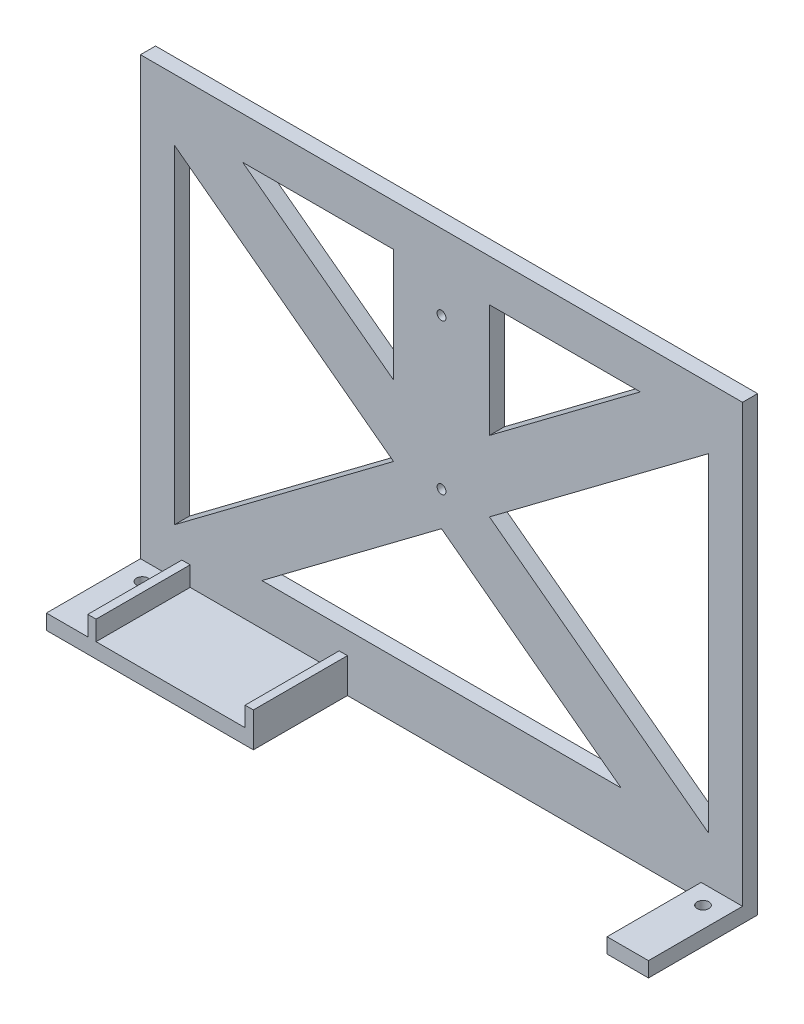
SolidWorks part; units mm, degrees
ref_plane "Front" through (0, 0, 0) normal (0, 0, 1) x (1, 0, 0)
ref_plane "Top" through (0, 0, 0) normal (0, 1, 0) x (1, 0, 0)
ref_plane "Right" through (0, 0, 0) normal (1, 0, 0) x (0, 0, -1)
sketch "Sketch1" plane through (0, 0, 0) normal (0, 0, 1) x (1, 0, 0)
  line L0 (-90.1289, 55.4552) -> (-90.1289, -55.4552)
  line L1 (-101.6, 76.2) -> (101.6, 76.2)
  line L2 (-101.6, 76.2) -> (-101.6, -76.2)
  line L3 (-101.6, -76.2) -> (101.6, -76.2)
  line L4 (101.6, 76.2) -> (101.6, -76.2)
  line L5 (-101.6, 76.2) -> (101.6, -76.2) construction
  line L6 (-101.6, -76.2) -> (101.6, 76.2) construction
  line L7 (0, -55) -> (0, 55) construction
  line L8 (-90.1289, -55.4552) -> (-16.1887, 0)
  line L9 (-16.1887, 0) -> (-90.1289, 55.4552)
  line L10 (55, 0) -> (-55, 0) construction
  line L11 (16.1887, 0) -> (90.1289, 55.4552)
  line L12 (90.1289, -55.4552) -> (16.1887, 0)
  line L13 (90.1289, 55.4552) -> (90.1289, -55.4552)
  line L14 (-16.1887, 61.9912) -> (-16.1887, 23.8125)
  line L15 (-16.1887, 23.8125) -> (-67.0937, 61.9912)
  line L16 (-67.0937, 61.9912) -> (-16.1887, 61.9912)
  line L17 (16.1887, 23.8125) -> (67.0937, 61.9912)
  line L18 (16.1887, 61.9912) -> (16.1887, 23.8125)
  line L19 (67.0937, 61.9912) -> (16.1887, 61.9912)
  line L20 (-60.6282, -57.0175) -> (0, -11.5463)
  line L21 (0, -11.5463) -> (60.6282, -57.0175)
  line L22 (60.6282, -57.0175) -> (-60.6282, -57.0175)
  circle A0 centre (0, 50.8) radius 1.5
  circle A2 centre (0, 0) radius 1.5
  point P0 (0, 0)
  dimension "D3" = 3
  dimension "D4" = 50.8
  dimension "D6" = 19.05
  dimension "D1" = 203.2
  dimension "D2" = 152.4
  dimension "D5" = 25.4
extrude "Boss-Extrude1" add sketch "Sketch1" along normal blind 5.08 contours L4 L1 L2 L3 A2 A0 L19 L17 L18 L9 L8 L0 L11 L13 L12 L15 L16 L14 L21 L22 L20 region at (0, 73.66, 0)
sketch "Sketch2" plane through (0, 0, 5.08) normal (0, 0, 1) x (1, 0, 0)
  line L0 (-101.6, -76.2) -> (101.6, -76.2) construction
  line L1 (-101.6, -76.2) -> (-87.63, -76.2)
  line L2 (-101.6, -76.2) -> (-101.6, -71.12)
  line L3 (-101.6, -71.12) -> (-87.63, -71.12)
  line L4 (-87.63, -76.2) -> (-87.63, -71.12)
  line L5 (0, -55) -> (0, 55) construction
  line L6 (101.6, -71.12) -> (87.63, -71.12)
  line L7 (87.63, -76.2) -> (87.63, -71.12)
  line L8 (101.6, -76.2) -> (87.63, -76.2)
  line L9 (101.6, -76.2) -> (101.6, -71.12)
  line L11 (-87.63, -71.12) -> (-31.75, -71.12)
  line L12 (-87.63, -71.12) -> (-87.63, -76.2)
  line L13 (-87.63, -76.2) -> (-31.75, -76.2)
  line L14 (-31.75, -71.12) -> (-31.75, -76.2)
  line L15 (-87.63, -71.12) -> (-84.836, -71.12)
  line L16 (-87.63, -71.12) -> (-87.63, -64.5258)
  line L17 (-87.63, -64.5258) -> (-84.836, -64.5258)
  line L18 (-84.836, -71.12) -> (-84.836, -64.5258)
  line L19 (-31.75, -71.12) -> (-34.544, -71.12)
  line L20 (-31.75, -71.12) -> (-31.75, -64.5258)
  line L21 (-31.75, -64.5258) -> (-34.544, -64.5258)
  line L22 (-34.544, -71.12) -> (-34.544, -64.5258)
  line M10 (-101.6, -76.2) -> (101.6, -76.2)
  dimension "D1" = 5.08
  dimension "D2" = 55.88
  dimension "D3" = 50.292
  dimension "D4" = 13.97
  dimension "D5" = 31.75
extrude "Boss-Extrude2" add sketch "Sketch2" along normal blind 31.75 contours L4 L3 L2 M10 | L14 L11 L4 M10 | L9 L6 L7 M10 | L16 L15 L18 L17 | L20 L19 L22 L21 region at (-94.615, -73.66, 5.08) region at (94.615, -73.66, 5.08) region at (-59.69, -73.66, 5.08)
sketch "Sketch3" plane through (0, -71.12, 0) normal (0, 1, 0) x (1, 0, 0)
  line L4 (0, -55) -> (0, 55) construction
  line L10 (-101.6, -5.08) -> (-87.63, -5.08) construction
  line L11 (-101.6, -36.83) -> (-101.6, -5.08) construction
  circle A0 centre (-94.615, -11.43) radius 2
  circle A1 centre (94.615, -11.43) radius 2
  dimension "D1" = 4
  dimension "D2" = 6.35
  dimension "D3" = 6.985
extrude "Cut-Extrude1" cut sketch "Sketch3" against normal up to vertex (5.08 mm away) contours A0 | A1 region at (-94.615, -71.12, 11.43) region at (94.615, -71.12, 11.43) up to point (-101.6, -76.2, 36.83)
